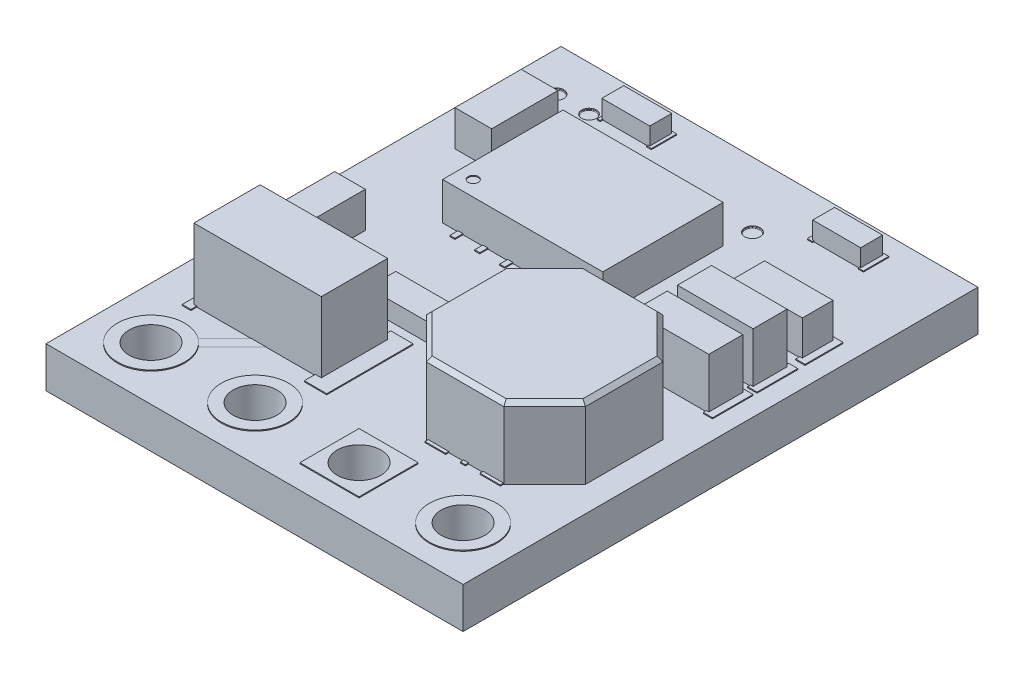
SolidWorks part; units mm, degrees
ref_plane "Front" through (0, 0, 0) normal (0, 0, 1) x (1, 0, 0)
ref_plane "Top" through (0, 0, 0) normal (0, 1, 0) x (1, 0, 0)
ref_plane "Right" through (0, 0, 0) normal (1, 0, 0) x (0, 0, -1)
sketch "Sketch1" plane through (0, 0, 0) normal (0, 1, 0) x (1, 0, 0)
  line L0 (-3.8862, -5.1054) -> (-1.2954, -5.1054) construction
  line L1 (-5.1943, 6.4135) -> (5.1943, 6.4135)
  line L2 (-5.1943, 6.4135) -> (-5.1943, -6.4135)
  line L3 (-5.1943, -6.4135) -> (5.1943, -6.4135)
  line L4 (5.1943, 6.4135) -> (5.1943, -6.4135)
  line L5 (-5.1943, 6.4135) -> (5.1943, -6.4135) construction
  line L6 (-5.1943, -6.4135) -> (5.1943, 6.4135) construction
  line L7 (-1.2954, -5.1054) -> (1.2954, -5.1054) construction
  line L8 (1.2954, -5.1054) -> (3.8862, -5.1054) construction
  line L9 (0, -5.1054) -> (0, 0) construction
  circle A0 centre (-3.8862, -5.1054) radius 0.5461
  circle A1 centre (-1.2954, -5.1054) radius 0.5461
  circle A2 centre (1.2954, -5.1054) radius 0.5461
  circle A3 centre (3.8862, -5.1054) radius 0.5461
  point P0 (0, 0)
  dimension "D3" = 1.0922
  dimension "D1" = 10.3886
  dimension "D2" = 12.827
  dimension "D4" = 0.762
  dimension "D5" = 0.762
extrude "Boss-Extrude1" add sketch "Sketch1" along normal blind 1.016
sketch "Sketch2" plane through (0, 1.016, 0) normal (0, 1, 0) x (1, 0, 0)
  line L0 (-5.1943, -6.4135) -> (5.1943, -6.4135) construction
  line L1 (3.5433, 0.2159) -> (4.5593, -0.8001)
  line L2 (0.5969, -0.8001) -> (1.6129, 0.2159)
  line L3 (0.5969, -2.7305) -> (1.6129, -3.7465)
  line L4 (3.5433, -3.7465) -> (4.5593, -2.7305)
  line L5 (5.1943, -6.4135) -> (5.1943, 6.4135) construction
  line L9 (1.6129, -3.7465) -> (3.5433, -3.7465)
  line L11 (0.5969, -2.7305) -> (0.5969, -0.8001)
  line L12 (1.6129, 0.2159) -> (3.5433, 0.2159)
  line L13 (4.5593, -2.7305) -> (4.5593, -0.8001)
  line L14 (0.5969, -3.7465) -> (4.5593, 0.2159) construction
  line L15 (0.5969, 0.2159) -> (4.5593, -3.7465) construction
  point P0 (2.5781, -1.7653)
  dimension "D1" = 2.667
  dimension "D2" = 3.9624
  dimension "D3" = 0.635
extrude "Boss-Extrude2" add sketch "Sketch2" along normal blind 1.778
sketch "Sketch3" plane through (0, 1.016, 0) normal (0, 1, 0) x (1, 0, 0)
  line L0 (5.1943, 6.4135) -> (-5.1943, 6.4135) construction
  line L1 (-2.8575, 4.1275) -> (1.1303, 4.1275)
  line L2 (-2.8575, 4.1275) -> (-2.8575, 1.1303)
  line L3 (-2.8575, 1.1303) -> (1.1303, 1.1303)
  line L4 (1.1303, 4.1275) -> (1.1303, 1.1303)
  line L5 (-2.8575, 4.1275) -> (1.1303, 1.1303) construction
  line L6 (-2.8575, 1.1303) -> (1.1303, 4.1275) construction
  line L7 (-5.1943, 6.4135) -> (-5.1943, -6.4135) construction
  point P0 (-0.8636, 2.6289)
  dimension "D1" = 2.9972
  dimension "D2" = 2.286
  dimension "D3" = 3.9878
  dimension "D4" = 2.3368
extrude "Boss-Extrude3" add sketch "Sketch3" along normal blind 0.9398
sketch "Sketch9" plane through (0, 1.9558, 0) normal (0, 1, 0) x (1, 0, 0)
  line L0 (-2.8575, 4.1275) -> (-2.8575, 1.1303) construction
  line L1 (-2.8575, 1.1303) -> (1.1303, 1.1303) construction
  circle A0 centre (-2.4765, 1.5113) radius 0.127
  dimension "D1" = 0.254
  dimension "D2" = 0.381
  dimension "D3" = 0.381
extrude "Cut-Extrude1" cut sketch "Sketch9" against normal blind 0.0254
sketch "Sketch10" plane through (0, 1.016, 0) normal (0, 1, 0) x (1, 0, 0)
  line L0 (1.1303, 4.1275) -> (-2.8575, 4.1275) construction
  line L1 (-2.4765, 4.1275) -> (-2.3495, 4.1275)
  line L2 (-2.4765, 4.1275) -> (-2.4765, 4.3307)
  line L3 (-2.4765, 4.3307) -> (-2.3495, 4.3307)
  line L4 (-2.3495, 4.1275) -> (-2.3495, 4.3307)
  line L5 (-1.8567, 4.1275) -> (-1.8567, 4.3307)
  line L6 (-1.8567, 4.1275) -> (-1.7297, 4.1275)
  line L7 (-1.7297, 4.1275) -> (-1.7297, 4.3307)
  line L8 (-1.8567, 4.3307) -> (-1.7297, 4.3307)
  line L9 (-1.237, 4.1275) -> (-1.237, 4.3307)
  line L10 (-1.237, 4.1275) -> (-1.11, 4.1275)
  line L11 (-1.11, 4.1275) -> (-1.11, 4.3307)
  line L12 (-1.237, 4.3307) -> (-1.11, 4.3307)
  line L13 (-0.6172, 4.1275) -> (-0.6172, 4.3307)
  line L14 (-0.6172, 4.1275) -> (-0.4902, 4.1275)
  line L15 (-0.4902, 4.1275) -> (-0.4902, 4.3307)
  line L16 (-0.6172, 4.3307) -> (-0.4902, 4.3307)
  line L17 (0.0025, 4.1275) -> (0.0025, 4.3307)
  line L18 (0.0025, 4.1275) -> (0.1295, 4.1275)
  line L19 (0.1295, 4.1275) -> (0.1295, 4.3307)
  line L20 (0.0025, 4.3307) -> (0.1295, 4.3307)
  line L21 (0.6223, 4.1275) -> (0.6223, 4.3307)
  line L22 (0.6223, 4.1275) -> (0.7493, 4.1275)
  line L23 (0.7493, 4.1275) -> (0.7493, 4.3307)
  line L24 (0.6223, 4.3307) -> (0.7493, 4.3307)
  line L25 (-2.8575, 4.1275) -> (-2.8575, 1.1303) construction
  line L26 (1.1303, 1.1303) -> (1.1303, 4.1275) construction
  line L27 (-2.8575, 2.6289) -> (1.1303, 2.6289) construction
  line L28 (-2.8575, 4.1275) -> (-2.8575, 1.1303) construction
  line L29 (0.6223, 0.9271) -> (0.7493, 0.9271)
  line L30 (0.7493, 1.1303) -> (0.7493, 0.9271)
  line L31 (0.6223, 1.1303) -> (0.7493, 1.1303)
  line L32 (0.6223, 1.1303) -> (0.6223, 0.9271)
  line L33 (0.0025, 0.9271) -> (0.1295, 0.9271)
  line L34 (0.1295, 1.1303) -> (0.1295, 0.9271)
  line L35 (0.0025, 1.1303) -> (0.1295, 1.1303)
  line L36 (0.0025, 1.1303) -> (0.0025, 0.9271)
  line L37 (-0.6172, 0.9271) -> (-0.4902, 0.9271)
  line L38 (-0.4902, 1.1303) -> (-0.4902, 0.9271)
  line L39 (-0.6172, 1.1303) -> (-0.4902, 1.1303)
  line L40 (-0.6172, 1.1303) -> (-0.6172, 0.9271)
  line L41 (-1.237, 0.9271) -> (-1.11, 0.9271)
  line L42 (-1.11, 1.1303) -> (-1.11, 0.9271)
  line L43 (-1.237, 1.1303) -> (-1.11, 1.1303)
  line L44 (-1.237, 1.1303) -> (-1.237, 0.9271)
  line L45 (-1.8567, 0.9271) -> (-1.7297, 0.9271)
  line L46 (-1.7297, 1.1303) -> (-1.7297, 0.9271)
  line L47 (-1.8567, 1.1303) -> (-1.7297, 1.1303)
  line L48 (-1.8567, 1.1303) -> (-1.8567, 0.9271)
  line L49 (-2.3495, 1.1303) -> (-2.3495, 0.9271)
  line L50 (-2.4765, 0.9271) -> (-2.3495, 0.9271)
  line L51 (-2.4765, 1.1303) -> (-2.4765, 0.9271)
  line L52 (-2.4765, 1.1303) -> (-2.3495, 1.1303)
  dimension "D2" = 0.381
  dimension "D3" = 0.127
  dimension "D4" = 0.381
  dimension "D5" = 0.2032
  dimension "D1" = 6
extrude "Boss-Extrude9" add sketch "Sketch10" along normal blind 0.0254
sketch "Sketch4" plane through (0, 1.016, 0) normal (0, 1, 0) x (1, 0, 0)
  line L0 (4.5593, -2.7305) -> (4.5593, -0.8001) construction
  line L1 (2.6771, 1.1906) -> (4.5593, 1.1906)
  line L2 (2.6771, 1.1906) -> (2.6771, 0.3429)
  line L3 (2.6771, 0.3429) -> (4.5593, 0.3429)
  line L4 (4.5593, 1.1906) -> (4.5593, 0.3429)
  line L5 (2.6771, 1.1906) -> (4.5593, 0.3429) construction
  line L6 (2.6771, 0.3429) -> (4.5593, 1.1906) construction
  line L7 (2.6771, 2.2923) -> (4.5593, 2.2923)
  line L8 (2.6771, 2.2923) -> (2.6771, 1.4446)
  line L9 (2.6771, 1.4446) -> (4.5593, 1.4446)
  line L10 (4.5593, 2.2923) -> (4.5593, 1.4446)
  line L11 (2.6771, 2.2923) -> (4.5593, 1.4446) construction
  line L12 (2.6771, 1.4446) -> (4.5593, 2.2923) construction
  line L13 (3.5433, 0.2159) -> (1.6129, 0.2159) construction
  point P0 (3.6182, 0.7667)
  point P5 (3.6182, 1.8684)
  dimension "D1" = 0.127
  dimension "D2" = 0.254
extrude "Boss-Extrude4" add sketch "Sketch4" along normal blind 1.27
sketch "Sketch5" plane through (0, 1.016, 0) normal (0, 1, 0) x (1, 0, 0)
  line L0 (4.5593, -2.7305) -> (4.5593, -0.8001) construction
  line L1 (-4.4222, 0.0062) -> (-3.6602, 0.0062)
  line L2 (-4.4222, 0.0062) -> (-4.4222, -1.6956)
  line L3 (-4.4222, -1.6956) -> (-3.6602, -1.6956)
  line L4 (-3.6602, 0.0062) -> (-3.6602, -1.6956)
  line L5 (-4.4222, 0.0062) -> (-3.6602, -1.6956) construction
  line L6 (-4.4222, -1.6956) -> (-3.6602, 0.0062) construction
  line L7 (-4.3058, 4.5352) -> (-3.3914, 4.5352)
  line L8 (-4.3058, 4.5352) -> (-4.3058, 2.8842)
  line L9 (-4.3058, 2.8842) -> (-3.3914, 2.8842)
  line L10 (-3.3914, 4.5352) -> (-3.3914, 2.8842)
  line L11 (-4.3058, 4.5352) -> (-3.3914, 2.8842) construction
  line L12 (-4.3058, 2.8842) -> (-3.3914, 4.5352) construction
  line L13 (2.8575, 3.4353) -> (4.5593, 3.4353)
  line L14 (2.8575, 3.4353) -> (2.8575, 2.6733)
  line L15 (2.8575, 2.6733) -> (4.5593, 2.6733)
  line L16 (4.5593, 3.4353) -> (4.5593, 2.6733)
  line L17 (2.8575, 3.4353) -> (4.5593, 2.6733) construction
  line L18 (2.8575, 2.6733) -> (4.5593, 3.4353) construction
  line L19 (4.5593, 2.2923) -> (2.6771, 2.2923) construction
  point P0 (-4.0412, -0.8447)
  point P5 (-3.8486, 3.7097)
  point P10 (3.7084, 3.0543)
  dimension "D1" = 0.762
  dimension "D2" = 0.9144
  dimension "D3" = 1.7018
  dimension "D4" = 1.651
  dimension "D5" = 0.381
extrude "Boss-Extrude5" add sketch "Sketch5" along normal blind 0.889
sketch "Sketch6" plane through (0, 1.016, 0) normal (0, 1, 0) x (1, 0, 0)
  line L1 (-3.1083, 5.8915) -> (-1.9136, 5.8915)
  line L2 (-3.1083, 5.8915) -> (-3.1083, 5.3462)
  line L3 (-3.1083, 5.3462) -> (-1.9136, 5.3462)
  line L4 (-1.9136, 5.8915) -> (-1.9136, 5.3462)
  line L5 (-3.1083, 5.8915) -> (-1.9136, 5.3462) construction
  line L6 (-3.1083, 5.3462) -> (-1.9136, 5.8915) construction
  line L7 (2.1444, 5.8915) -> (3.3391, 5.8915)
  line L8 (2.1444, 5.8915) -> (2.1444, 5.3462)
  line L9 (2.1444, 5.3462) -> (3.3391, 5.3462)
  line L10 (3.3391, 5.8915) -> (3.3391, 5.3462)
  line L11 (2.1444, 5.8915) -> (3.3391, 5.3462) construction
  line L12 (2.1444, 5.3462) -> (3.3391, 5.8915) construction
  line L13 (-1.9412, -0.9545) -> (-0.3846, -0.9545)
  line L14 (-1.9412, -0.9545) -> (-1.9412, -1.6457)
  line L15 (-1.9412, -1.6457) -> (-0.3846, -1.6457)
  line L16 (-0.3846, -0.9545) -> (-0.3846, -1.6457)
  line L17 (-1.9412, -0.9545) -> (-0.3846, -1.6457) construction
  line L18 (-1.9412, -1.6457) -> (-0.3846, -0.9545) construction
  point P0 (-2.5109, 5.6188)
  point P5 (2.7418, 5.6188)
  point P10 (-1.1629, -1.3001)
extrude "Boss-Extrude6" add sketch "Sketch6" along normal blind 0.4572
sketch "Sketch7" plane through (0, 1.016, 0) normal (0, 1, 0) x (1, 0, 0)
  line L0 (-5.1943, -6.4135) -> (5.1943, -6.4135) construction
  line L1 (-4.1783, -2.0955) -> (-1.0033, -2.0955)
  line L2 (-4.1783, -2.0955) -> (-4.1783, -3.7465)
  line L3 (-4.1783, -3.7465) -> (-1.0033, -3.7465)
  line L4 (-1.0033, -2.0955) -> (-1.0033, -3.7465)
  line L5 (-4.1783, -2.0955) -> (-1.0033, -3.7465) construction
  line L6 (-4.1783, -3.7465) -> (-1.0033, -2.0955) construction
  line L7 (-5.1943, 6.4135) -> (-5.1943, -6.4135) construction
  point P0 (-2.5908, -2.921)
  dimension "D1" = 1.651
  dimension "D2" = 3.175
  dimension "D3" = 2.667
  dimension "D4" = 1.016
extrude "Boss-Extrude7" add sketch "Sketch7" along normal blind 1.778
sketch "Sketch8" plane through (0, 1.016, 0) normal (0, 1, 0) x (1, 0, 0)
  line L1 (0.5588, -4.3688) -> (2.032, -4.3688)
  line L2 (0.5588, -4.3688) -> (0.5588, -5.842)
  line L3 (0.5588, -5.842) -> (2.032, -5.842)
  line L4 (2.032, -4.3688) -> (2.032, -5.842)
  line L5 (0.5588, -4.3688) -> (2.032, -5.842) construction
  line L6 (0.5588, -5.842) -> (2.032, -4.3688) construction
  line L7 (1.658, -3.4757) -> (2.1724, -3.4757)
  line L8 (1.658, -3.4757) -> (1.658, -3.8275)
  line L9 (1.658, -3.8275) -> (2.1724, -3.8275)
  line L10 (2.1724, -3.4757) -> (2.1724, -3.8275)
  line L11 (3.5364, -3.4757) -> (3.0286, -3.4757)
  line L12 (3.5364, -3.4757) -> (3.5364, -3.8275)
  line L13 (3.5364, -3.8275) -> (3.0286, -3.8275)
  line L14 (3.0286, -3.4757) -> (3.0286, -3.8275)
  line L15 (2.5414, -3.4757) -> (2.6661, -3.4757)
  line L16 (2.5414, -3.4757) -> (2.5414, -3.8275)
  line L17 (2.5414, -3.8275) -> (2.6661, -3.8275)
  line L18 (2.6661, -3.4757) -> (2.6661, -3.8275)
  line L19 (-1.1534, -1.8682) -> (-0.595, -1.8682)
  line L20 (-1.1534, -1.8682) -> (-1.1534, -4.02)
  line L21 (-1.1534, -4.02) -> (-0.595, -4.02)
  line L22 (-0.595, -1.8682) -> (-0.595, -4.02)
  line L23 (4.4977, 1.2733) -> (4.7297, 1.2733)
  line L24 (4.4977, 1.2733) -> (4.4977, 0.2664)
  line L25 (4.4977, 0.2664) -> (4.7297, 0.2664)
  line L26 (4.7297, 1.2733) -> (4.7297, 0.2664)
  line L27 (4.4977, 2.3883) -> (4.7297, 2.3883)
  line L28 (4.4977, 2.3883) -> (4.4977, 1.3735)
  line L29 (4.4977, 1.3735) -> (4.7297, 1.3735)
  line L30 (4.7297, 2.3883) -> (4.7297, 1.3735)
  line L31 (4.4977, 3.518) -> (4.7297, 3.518)
  line L32 (4.4977, 3.518) -> (4.4977, 2.5701)
  line L33 (4.4977, 2.5701) -> (4.7297, 2.5701)
  line L34 (4.7297, 3.518) -> (4.7297, 2.5701)
  line L35 (2.9004, 3.518) -> (2.7586, 3.518)
  line L36 (2.9004, 3.518) -> (2.9004, 2.6419)
  line L37 (2.9004, 2.6419) -> (2.7586, 2.6419)
  line L38 (2.7586, 3.518) -> (2.7586, 2.6419)
  line L39 (2.7114, 2.3883) -> (2.5414, 2.3883)
  line L40 (2.7114, 2.3883) -> (2.7114, 1.3735)
  line L41 (2.7114, 1.3735) -> (2.5414, 1.3735)
  line L42 (2.5414, 2.3883) -> (2.5414, 1.3735)
  line L43 (2.7114, 1.2733) -> (2.5414, 1.2733)
  line L44 (2.7114, 1.2733) -> (2.7114, 0.2664)
  line L45 (2.7114, 0.2664) -> (2.5414, 0.2664)
  line L46 (2.5414, 1.2733) -> (2.5414, 0.2664)
  line L47 (3.3099, 5.9425) -> (3.4423, 5.9425)
  line L48 (3.3099, 5.9425) -> (3.3099, 5.3113)
  line L49 (3.3099, 5.3113) -> (3.4423, 5.3113)
  line L50 (3.4423, 5.9425) -> (3.4423, 5.3113)
  line L51 (2.1724, 5.9425) -> (2.0447, 5.9425)
  line L52 (2.1724, 5.9425) -> (2.1724, 5.3113)
  line L53 (2.1724, 5.3113) -> (2.0447, 5.3113)
  line L54 (2.0447, 5.9425) -> (2.0447, 5.3113)
  line L55 (-1.9578, 5.9425) -> (-1.8394, 5.9425)
  line L56 (-1.9578, 5.9425) -> (-1.9578, 5.3113)
  line L57 (-1.9578, 5.3113) -> (-1.8394, 5.3113)
  line L58 (-1.8394, 5.9425) -> (-1.8394, 5.3113)
  line L59 (-3.0822, 5.9425) -> (-3.1571, 5.9425)
  line L60 (-3.0822, 5.9425) -> (-3.0822, 5.2782)
  line L61 (-3.0822, 5.2782) -> (-3.1571, 5.2782)
  line L62 (-3.1571, 5.9425) -> (-3.1571, 5.2782)
  line L63 (-4.1036, -1.9226) -> (-4.3193, -1.9226)
  line L64 (-4.1036, -1.9226) -> (-4.1036, -3.8948)
  line L65 (-4.1036, -3.8948) -> (-4.3193, -3.8948)
  line L66 (-4.3193, -1.9226) -> (-4.3193, -3.8948)
  circle A0 centre (-3.8862, -5.1054) radius 0.5461 construction
  circle A1 centre (-1.2954, -5.1054) radius 0.5461 construction
  circle A2 centre (1.2954, -5.1054) radius 0.5461 construction
  circle A3 centre (3.8862, -5.1054) radius 0.5461 construction
  circle A4 centre (-3.8862, -5.1054) radius 0.5461
  circle A5 centre (-1.2954, -5.1054) radius 0.5461
  circle A6 centre (1.2954, -5.1054) radius 0.5461
  circle A7 centre (3.8862, -5.1054) radius 0.5461
  circle A8 centre (-3.8862, -5.1054) radius 0.8382
  circle A9 centre (-1.2954, -5.1054) radius 0.8382
  circle A11 centre (3.8862, -5.1054) radius 0.8382
  dimension "D1" = 0.2921
extrude "Boss-Extrude8" add sketch "Sketch8" along normal blind 0.0254
chamfer "Chamfer1" distance 0.1016 angle 45 8 edges at (1.1049, 2.794, 0.2921) (2.5781, 2.794, -0.2159) (4.0513, 2.794, 0.2921) (4.5593, 2.794, 1.7653) (4.0513, 2.794, 3.2385) (0.5969, 2.794, 1.7653) (1.1049, 2.794, 3.2385) (2.5781, 2.794, 3.7465)
sketch "Sketch11" plane through (0, 0, 0) normal (0, -1, 0) x (1, 0, 0)
  line L0 (0.5588, 5.842) -> (2.032, 5.842) construction
  line L1 (0.5588, 4.3688) -> (0.5588, 5.842) construction
  line L2 (2.032, 4.3688) -> (0.5588, 4.3688) construction
  line L3 (2.032, 5.842) -> (2.032, 4.3688) construction
  line L4 (0.5588, 5.842) -> (2.032, 5.842)
  line L5 (0.5588, 4.3688) -> (0.5588, 5.842)
  line L6 (2.032, 4.3688) -> (0.5588, 4.3688)
  line L7 (2.032, 5.842) -> (2.032, 4.3688)
  circle A0 centre (3.8862, 5.1054) radius 0.5461 construction
  circle A1 centre (1.2954, 5.1054) radius 0.5461 construction
  circle A2 centre (-1.2954, 5.1054) radius 0.5461 construction
  circle A3 centre (-3.8862, 5.1054) radius 0.5461 construction
  circle A4 centre (-3.8862, 5.1054) radius 0.8382 construction
  circle A5 centre (-1.2954, 5.1054) radius 0.8382 construction
  circle A6 centre (3.8862, 5.1054) radius 0.8382 construction
  circle A7 centre (3.8862, 5.1054) radius 0.5461
  circle A8 centre (1.2954, 5.1054) radius 0.5461
  circle A9 centre (-1.2954, 5.1054) radius 0.5461
  circle A10 centre (-3.8862, 5.1054) radius 0.5461
  circle A11 centre (-3.8862, 5.1054) radius 0.8382
  circle A12 centre (-1.2954, 5.1054) radius 0.8382
  circle A13 centre (3.8862, 5.1054) radius 0.8382
extrude "Boss-Extrude10" add sketch "Sketch11" along normal blind 0.0025
sketch "Sketch12" plane through (0, 0, 0) normal (0, -1, 0) x (1, 0, 0)
  line L0 (2.1093, -1.1641) -> (-2.1093, -1.1641) construction
  line L1 (-4.5593, -2.267) -> (-2.0193, -2.267)
  line L2 (-4.5593, -2.267) -> (-4.5593, -5.8358)
  line L3 (-4.5593, -5.8358) -> (-2.0193, -5.8358)
  line L4 (-2.0193, -2.267) -> (-2.0193, -5.8358)
  line L5 (-4.5593, -2.267) -> (-2.0193, -5.8358) construction
  line L6 (-4.5593, -5.8358) -> (-2.0193, -2.267) construction
  line L7 (0, -1.1641) -> (0, 0) construction
  line L8 (4.4745, 4.1862) -> (4.4745, -0.9854) construction
  line L9 (1.923, 4.1862) -> (1.923, -0.3926) construction
  line L10 (-0.6688, 4.1862) -> (-0.6688, 0.9904) construction
  line L11 (-3.4045, 4.1862) -> (-3.4045, -0.3926) construction
  line L12 (-5.1943, -6.4135) -> (-5.1943, 6.4135) construction
  line L13 (4.4745, -5.376) -> (0.8254, -5.376) construction
  line L14 (4.4745, -4.1855) -> (0.5703, -4.1855) construction
  text T0 "Pololu" font "Century Gothic" height 1.016
  text T1 "VOUT" font "Century Gothic" height 1.016
  text T2 "GND" font "Century Gothic" height 1.016
  text T3 "VIN" font "Century Gothic" height 1.016
  text T4 "SHDN" font "Century Gothic" height 1.016
  text T5 "0J7990" font "Century Gothic" height 0.762
  text T6 "reg 16a" font "Century Gothic" height 0.762
  point P0 (-3.2893, -4.0514)
  dimension "D1" = 0.635
  dimension "D2" = 2.54
extrude "Boss-Extrude11" add sketch "Sketch12" along normal blind 0.0025
sketch "Sketch13" plane through (0, 1.016, 0) normal (0, 1, 0) x (1, 0, 0)
  circle A8 centre (-2.1635, -1.757) radius 0.1888
  circle A9 centre (-3.4256, -1.0735) radius 0.1843
  circle A10 centre (1.2003, 4.7893) radius 0.193
  circle A11 centre (0.0226, 4.8274) radius 0.1866
  circle A12 centre (-2.6368, 4.0066) radius 0.1857
  circle A13 centre (-4.2226, 5.3244) radius 0.1899
  circle A14 centre (-3.3824, 5.3014) radius 0.1822
extrude "Cut-Extrude2" cut sketch "Sketch13" against normal blind 0.0381
sketch "Sketch14" plane through (0, -0.0025, 0) normal (0, -1, 0) x (1, 0, 0)
  circle A0 centre (-3.3824, -5.3014) radius 0.1822 construction
  circle A1 centre (-4.2226, -5.3244) radius 0.1899 construction
  circle A2 centre (0.0226, -4.8274) radius 0.1866 construction
  circle A3 centre (1.2003, -4.7893) radius 0.193 construction
  circle A4 centre (-3.4256, 1.0735) radius 0.1843 construction
  circle A5 centre (-2.1635, 1.757) radius 0.1888 construction
  circle A6 centre (-3.3824, -5.3014) radius 0.1822
  circle A7 centre (-4.2226, -5.3244) radius 0.1899
  circle A8 centre (0.0226, -4.8274) radius 0.1866
  circle A9 centre (1.2003, -4.7893) radius 0.193
  circle A10 centre (-3.4256, 1.0735) radius 0.1843
  circle A11 centre (-2.1635, 1.757) radius 0.1888
  circle A13 centre (-2.6368, -4.0066) radius 0.1857 construction
  circle A14 centre (-2.6368, -4.0066) radius 0.1857
extrude "Cut-Extrude3" cut sketch "Sketch14" against normal blind 0.0381
fillet "Fillet1" radius 0.0152 13 edges at (-2.1635, 0.9779, 1.9458) (-3.4256, 0.9779, 1.2578) (1.2003, 0.9779, -4.5964) (0.0226, 0.9779, -4.6409) (-3.3824, 0.9779, -5.1192) (-4.2226, 0.9779, -5.1345) (-3.4256, 0.0356, 0.8893) (-2.1635, 0.0356, 1.5682) (-4.2226, 0.0356, -5.5143) (-3.3824, 0.0356, -5.4836) (-2.6368, 0.0356, -4.1923) (0.0226, 0.0356, -5.014) (1.2003, 0.0356, -4.9823)
sketch "Sketch15" plane through (0, 1.016, 0) normal (0, 1, 0) x (1, 0, 0)
  line L0 (-2.5339, -3.5421) -> (-3.4145, -4.414)
  line L1 (-3.2302, -4.5913) -> (-2.1748, -3.5365)
  line L2 (-2.5339, -3.5421) -> (-2.1748, -3.5365)
  arc A1 (-3.2302, -4.5913) -> (-3.4145, -4.414) centre (-3.9052, -5.1084) ccw
extrude "Boss-Extrude12" add sketch "Sketch15" along normal blind 0.0051
